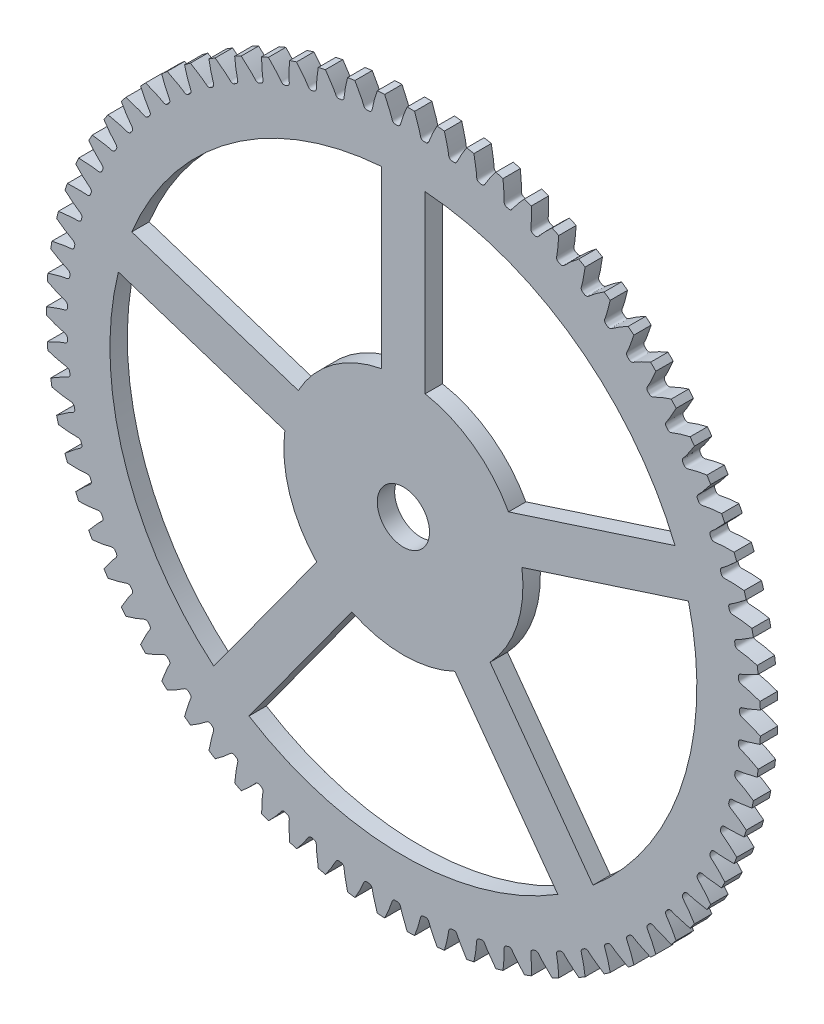
SolidWorks part; units mm, degrees
ref_plane "Alzado" through (0, 0, 0) normal (0, 0, 1) x (1, 0, 0)
ref_plane "Planta" through (0, 0, 0) normal (0, 1, 0) x (1, 0, 0)
ref_plane "Vista lateral" through (0, 0, 0) normal (1, 0, 0) x (0, 0, -1)
ref_axis "Eje1" through (0, 0, 55) along (0, 0, -1)
sketch "SketchRevolveEngranaje Abajo(8.2)" plane through (0, 0, 0) normal (1, 0, 0) x (0, 0, -1)
  line L0 (0, 0) -> (1, 0) construction
  line L1 (-0.1, 0) -> (-0.1, 4.1067)
  line L2 (-0.1, 4.1067) -> (0.1, 4.1067)
  line L3 (0.1, 4.1067) -> (0.1, 0)
  line L4 (0.1, 0) -> (-0.1, 0)
revolve "Engranaje Abajo(8.2)" add sketch "SketchRevolveEngranaje Abajo(8.2)" angle 360 about L0
sketch "SketchToothEngranaje Abajo(8.2)" plane through (0, 0, 0) normal (0, 0, 1) x (1, 0, 0)
  arc A0 (4.1099, 0.1321) -> (4.1099, -0.1321) centre (0, 0) cw
  spline S0 degree 3 poles (4.1099, -0.1321) (4.097, -0.1258) (4.0799, -0.1179) (4.0586, -0.1084) (4.0463, -0.103) (4.0342, -0.0979) (4.0224, -0.093) (4.0107, -0.0883) (3.9993, -0.0838) (3.9882, -0.0796) (3.9773, -0.0755) (3.9666, -0.0716) (3.9561, -0.0679) (3.946, -0.0644) (3.936, -0.0611) (3.9263, -0.058) (3.9158, -0.0548) (3.9079, -0.0519) (3.9021, -0.0506) (3.8998, -0.0499) (3.8975, -0.0492) (3.8952, -0.0485) (3.8929, -0.0476) (3.8906, -0.0466) (3.8882, -0.0455) (3.8858, -0.0441) (3.8832, -0.0425) (3.8805, -0.0405) (3.8776, -0.038) (3.8746, -0.0347) (3.8716, -0.0305) (3.8689, -0.0252) (3.8671, -0.019) (3.8664, -0.0105) (3.8668, 0) (3.8664, 0.0105) (3.8671, 0.019) (3.8689, 0.0252) (3.8716, 0.0305) (3.8746, 0.0347) (3.8776, 0.038) (3.8805, 0.0405) (3.8832, 0.0425) (3.8858, 0.0441) (3.8882, 0.0455) (3.8906, 0.0466) (3.8929, 0.0476) (3.8952, 0.0485) (3.8975, 0.0492) (3.8998, 0.0499) (3.9021, 0.0506) (3.9079, 0.0519) (3.9158, 0.0548) (3.9263, 0.058) (3.936, 0.0611) (3.946, 0.0644) (3.9561, 0.0679) (3.9666, 0.0716) (3.9773, 0.0755) (3.9882, 0.0796) (3.9993, 0.0838) (4.0107, 0.0883) (4.0224, 0.093) (4.0342, 0.0979) (4.0463, 0.103) (4.0586, 0.1084) (4.0799, 0.1179) (4.097, 0.1258) (4.1099, 0.1321) knots 0 0 0 0 0.073384 0.096841 0.119796 0.142248 0.164198 0.185645 0.20659 0.227033 0.246973 0.266411 0.285347 0.30378 0.321711 0.33914 0.356066 0.378146 0.382309 0.386424 0.390519 0.394627 0.398793 0.403073 0.407539 0.412287 0.417442 0.423165 0.42966 0.437164 0.44591 0.456039 0.467444 0.478762 0.5 0.521238 0.532556 0.543961 0.55409 0.562836 0.57034 0.576835 0.582558 0.587713 0.592461 0.596927 0.601207 0.605373 0.609481 0.613576 0.617691 0.621854 0.643934 0.66086 0.678289 0.69622 0.714653 0.733589 0.753027 0.772967 0.79341 0.814355 0.835802 0.857752 0.880204 0.903159 0.926616 1 1 1 1
extrude "ToothExtrudeCutEngranaje Abajo(8.2)" cut sketch "SketchToothEngranaje Abajo(8.2)" against normal blind 0.1 and the other way blind 0.1
pattern_circular "PatternEngranaje Abajo(8.2)" count 75 every 4.8 about axis through (0, 0, 55) along (0, 0, -1) of "ToothExtrudeCutEngranaje Abajo(8.2)"
sketch "AuxiliarySketchEngranaje Abajo(8.2)" plane through (0, 0, 0) normal (0, 0, 1) x (1, 0, 0)
  circle A0 centre (0, 0) radius 4 construction
  circle A1 centre (0, 0) radius 3.7588 construction
  circle A2 centre (0, 0) radius 3.8999 construction
  circle A3 centre (0, 0) radius 4.1067 construction
  circle A4 centre (0, 0) radius 3.8667 construction
  dimension "PitchDiameter" = 8
  dimension "BaseDiameter" = 7.5175
  dimension "FormDiameter" = 7.7999
  dimension "MajorDiameter" = 8.2133
  dimension "MinorDiameter" = 7.7333
sketch "Croquis5" plane through (0, 0, 0.1) normal (0, 0, 1) x (1, 0, 0)
  line L0 (0, 0) -> (0, 3.375) construction
  line L1 (0, 0) -> (-3.2098, 1.0429) construction
  line L2 (0, 0) -> (3.2098, 1.0429) construction
  line L3 (0, 0) -> (-1.9838, -2.7304) construction
  line L4 (0, 0) -> (1.9838, -2.7304) construction
  line L15 (1.3632, 0.1801) -> (3.2783, 0.8023)
  line L16 (0.997, -0.9469) -> (2.1806, -2.576)
  line L18 (0.5925, -1.2408) -> (1.7761, -2.8699)
  line L20 (-0.5925, -1.2408) -> (-1.7761, -2.8699)
  line L22 (-0.997, -0.9469) -> (-2.1806, -2.576)
  line L24 (-1.3632, 0.1801) -> (-3.2783, 0.8023)
  line L26 (-1.2087, 0.6556) -> (-3.1237, 1.2778)
  line L28 (-0.25, 1.3521) -> (-0.25, 3.3657)
  line L30 (0.25, 1.3521) -> (0.25, 3.3657)
  line L32 (1.2087, 0.6556) -> (3.1237, 1.2778)
  circle A0 centre (0, 0) radius 0.3
  arc A1 (-1.3632, 0.1801) -> (-0.997, -0.9469) centre (0, 0) ccw
  arc A2 (-3.2783, 0.8023) -> (-2.1806, -2.576) centre (0, 0) ccw
  arc A3 (-1.7761, -2.8699) -> (1.7761, -2.8699) centre (0, 0) ccw
  arc A4 (2.1806, -2.576) -> (3.2783, 0.8023) centre (0, 0) ccw
  arc A5 (3.1237, 1.2778) -> (0.25, 3.3657) centre (0, 0) ccw
  arc A6 (-0.25, 3.3657) -> (-3.1237, 1.2778) centre (0, 0) ccw
  arc A7 (0.997, -0.9469) -> (1.3632, 0.1801) centre (0, 0) ccw
  arc A8 (-0.5925, -1.2408) -> (0.5925, -1.2408) centre (0, 0) ccw
  arc A9 (1.2087, 0.6556) -> (0.25, 1.3521) centre (0, 0) ccw
  arc A10 (-0.25, 1.3521) -> (-1.2087, 0.6556) centre (0, 0) ccw
  point P9 (0.0773, 0.2378)
  point P12 (-0.2023, 0.1469)
  point P14 (-0.2023, -0.1469)
  point P16 (0.0773, -0.2378)
  point P18 (0.25, 0)
  point P20 (-0.0773, -0.2378)
  point P22 (0.2023, -0.1469)
  point P24 (0.2023, 0.1469)
  point P26 (-0.0773, 0.2378)
  point P28 (-0.25, 0)
  dimension "D1" = 0.6
  dimension "D2" = 6.75
  dimension "D3" = 2.75
  dimension "D4" = 72
  dimension "D5" = 72
  dimension "D6" = 72
  dimension "D7" = 72
  dimension "D8" = 0.25
  dimension "D9" = 0.25
  dimension "D10" = 0.25
  dimension "D11" = 0.5
  dimension "D12" = 0.5
  dimension "D13" = 0.5
  dimension "D14" = 0.5
  dimension "D15" = 0.25
  dimension "D16" = 0.5
  dimension "D17" = 0.25
extrude "Cortar-Extruir2" cut sketch "Croquis5" against normal up to next
